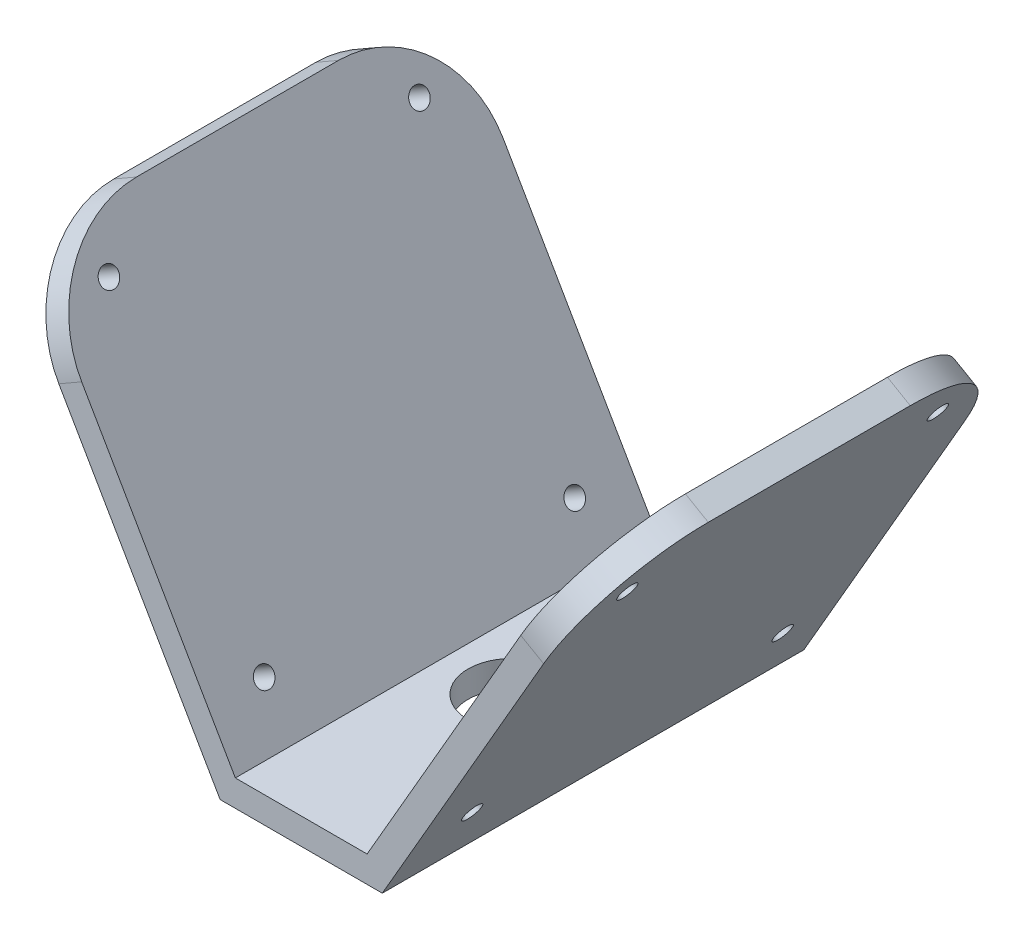
SolidWorks part; units mm, degrees
material "6061-O (SS)"
ref_plane "Plan de face" through (0, 0, 0) normal (0, 0, 1) x (1, 0, 0)
ref_plane "Plan de dessus" through (0, 0, 0) normal (0, 1, 0) x (1, 0, 0)
ref_plane "Plan de droite" through (0, 0, 0) normal (1, 0, 0) x (0, 0, -1)
sketch "Esquisse1" plane through (0, 0, 0) normal (0, 0, 1) x (1, 0, 0)
  line L0 (15, 0) -> (-15, 0)
  line L6 (-18.4641, -6) -> (18.4641, -6)
  line L7 (0, -6) -> (0, 0) construction
  line L12 (-15, 0) -> (-62.5, 82.2724)
  line L13 (-62.5, 82.2724) -> (-67.6962, 79.2724)
  line L17 (-67.6962, 79.2724) -> (-18.4641, -6)
  line L18 (-15, 0) -> (-15, 27.1769) construction
  line L20 (67.6962, 79.2724) -> (18.4641, -6)
  line L21 (62.5, 82.2724) -> (67.6962, 79.2724)
  line L22 (15, 0) -> (62.5, 82.2724)
  dimension "D1" = 6
  dimension "D2" = 15
  dimension "D3" = 6
  dimension "D4" = 95
  dimension "D5" = 30
extrude "Boss.-Extru.1" add sketch "Esquisse1" along normal blind 48 and the other way blind 48
sketch "Esquisse2" plane through (-16.4462, -9.4952, 0) normal (-0.866, -0.5, 0) x (0, 0, 1)
  line L1 (0, 55) -> (-35.3553, 19.6447) construction
  line L2 (0, 55) -> (0, 0) construction
  line L3 (0, 55) -> (35.3553, 90.3553) construction
  line L4 (0, 55) -> (32.5177, 55) construction
  line L5 (-48, 102.5) -> (48, 102.5) construction
  line L6 (48, 102.5) -> (48, 4.0359) construction
  line L7 (30, 102.5) -> (48, 102.5) construction
  line L8 (48, 102.5) -> (48, 84.5) construction
  line L9 (35.3553, 90.3553) -> (40.3051, 95.3051) construction
  circle A0 centre (-35.3553, 19.6447) radius 2.2
  circle A1 centre (35.3553, 90.3553) radius 2.2
  circle A2 centre (35.3553, 19.6447) radius 2.2
  circle A3 centre (-35.3553, 90.3553) radius 2.2
  spline S0 degree 2 poles (30, 102.5) (35.8858, 99.6427) (40.3051, 95.3051) knots 0 0 0 0.486514 0.486514 0.486514 construction
  spline S1 degree 2 poles (40.3051, 95.3051) (44.9694, 90.727) (48, 84.5) knots 0.486514 0.486514 0.486514 1 1 1 construction
  point P21 (40.5765, 95.4529)
  point P23 (40.5765, 95.5765)
  point P24 (0, 0)
  dimension "D3" = 4.4
  dimension "D6" = 4.4
  dimension "D1" = 45
  dimension "D2" = 50
  dimension "D4" = 45
  dimension "D5" = 50
  dimension "D7" = 55
  dimension "D8" = 18
  dimension "D9" = 18
  dimension "D10" = 7
extrude "Enlèv. mat.-Extru.1" cut sketch "Esquisse2" against normal blind 10
fillet "Congé1" radius 25 4 edges at (65.0981, 80.7724, 48) (65.0981, 80.7724, -48) (-65.0981, 80.7724, -48) (-65.0981, 80.7724, 48)
mirror "Symétrie1" about plane through (0, 0, 0) normal (1, 0, 0) of "Enlèv. mat.-Extru.1"
scale "Echelle1" scale about origin uniform scaling yes scale factor 0.5
sketch "Esquisse3" plane through (0, 0, 0) normal (0, 1, 0) x (1, 0, 0)
  circle A0 centre (0, 0) radius 5
  dimension "D1" = 10
extrude "Enlèv. mat.-Extru.2" cut sketch "Esquisse3" against normal blind 10
